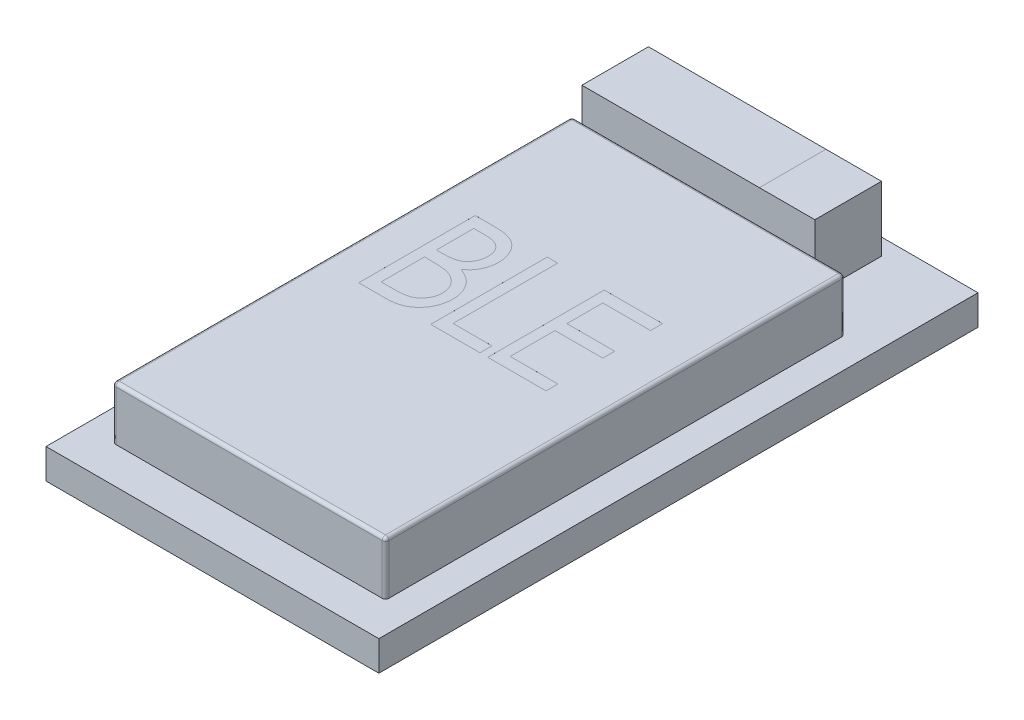
SolidWorks part; units mm, degrees
ref_plane "Piano frontale" through (0, 0, 0) normal (0, 0, 1) x (1, 0, 0)
ref_plane "Piano superiore" through (0, 0, 0) normal (0, 1, 0) x (1, 0, 0)
ref_plane "Piano destro" through (0, 0, 0) normal (1, 0, 0) x (0, 0, -1)
sketch "Schizzo1" plane through (0, 0, 0) normal (0, 1, 0) x (1, 0, 0)
  line L1 (-13.2216, 30.1798) -> (-3.2216, 30.1798)
  line L2 (-13.2216, 30.1798) -> (-13.2216, 12.1798)
  line L3 (-13.2216, 12.1798) -> (-3.2216, 12.1798)
  line L4 (-3.2216, 30.1798) -> (-3.2216, 12.1798)
  dimension "D1" = 10
  dimension "D2" = 18
extrude "Estrusione-Estrusione1" add sketch "Schizzo1" along normal blind 0.9
sketch "Schizzo2" plane through (0, 0.9, 0) normal (0, 1, 0) x (1, 0, 0)
  line L0 (-13.2216, 30.1798) -> (-13.2216, 12.1798) construction
  line L1 (-12.3216, 27.0798) -> (-4.1216, 27.0798)
  line L2 (-12.3216, 27.0798) -> (-12.3216, 13.2798)
  line L3 (-12.3216, 13.2798) -> (-4.1216, 13.2798)
  line L4 (-4.1216, 27.0798) -> (-4.1216, 13.2798)
  line L7 (-13.2216, 12.1798) -> (-3.2216, 12.1798) construction
  dimension "D1" = 8.2
  dimension "D2" = 13.8
  dimension "D3" = 0.9
  dimension "D4" = 1.1
extrude "Estrusione-Estrusione2" add sketch "Schizzo2" along normal blind 1.6
fillet "Raccordo1" radius 0.1 8 edges at (-8.2216, 2.5, -27.0798) (-12.3216, 2.5, -20.1798) (-8.2216, 2.5, -13.2798) (-4.1216, 2.5, -20.1798) (-4.1216, 1.7, -27.0798) (-12.3216, 1.7, -27.0798) (-4.1216, 1.7, -13.2798) (-12.3216, 1.7, -13.2798)
sketch "Schizzo3" plane through (0, 0.9, 0) normal (0, 1, 0) x (1, 0, 0)
  line L0 (-13.2216, 30.1798) -> (-13.2216, 12.1798) construction
  line L1 (-12.6216, 29.6798) -> (-5.6216, 29.6798)
  line L2 (-12.6216, 29.6798) -> (-12.6216, 27.6798)
  line L3 (-12.6216, 27.6798) -> (-5.6216, 27.6798)
  line L4 (-5.6216, 29.6798) -> (-5.6216, 27.6798)
  line L6 (-3.2216, 30.1798) -> (-13.2216, 30.1798) construction
  dimension "D1" = 2
  dimension "D2" = 7
  dimension "D3" = 0.6
  dimension "D4" = 0.5
extrude "Estrusione-Estrusione3" add sketch "Schizzo3" along normal blind 1.95
sketch "Schizzo4" plane through (0, 2.85, 0) normal (0, 1, 0) x (1, 0, 0)
  line L0 (-12.6216, 27.6798) -> (-5.6216, 27.6798) construction
  line L1 (-5.6216, 29.6798) -> (-7.2897, 29.6798)
  line L2 (-5.6216, 29.6798) -> (-5.6216, 27.6798)
  line L3 (-5.6216, 27.6798) -> (-7.2897, 27.6798)
  line L4 (-7.2897, 29.6798) -> (-7.2897, 27.6798)
extrude "Estrusione-Estrusione4" add sketch "Schizzo4" along normal blind 0.0001
sketch "Schizzo6" plane through (0, 2.5, 0) normal (0, 1, 0) x (1, 0, 0)
  text T0 "BLE" font "Century Gothic" height 3.5
extrude "Taglio-Estrusione1" cut sketch "Schizzo6" against normal blind 0.0001
